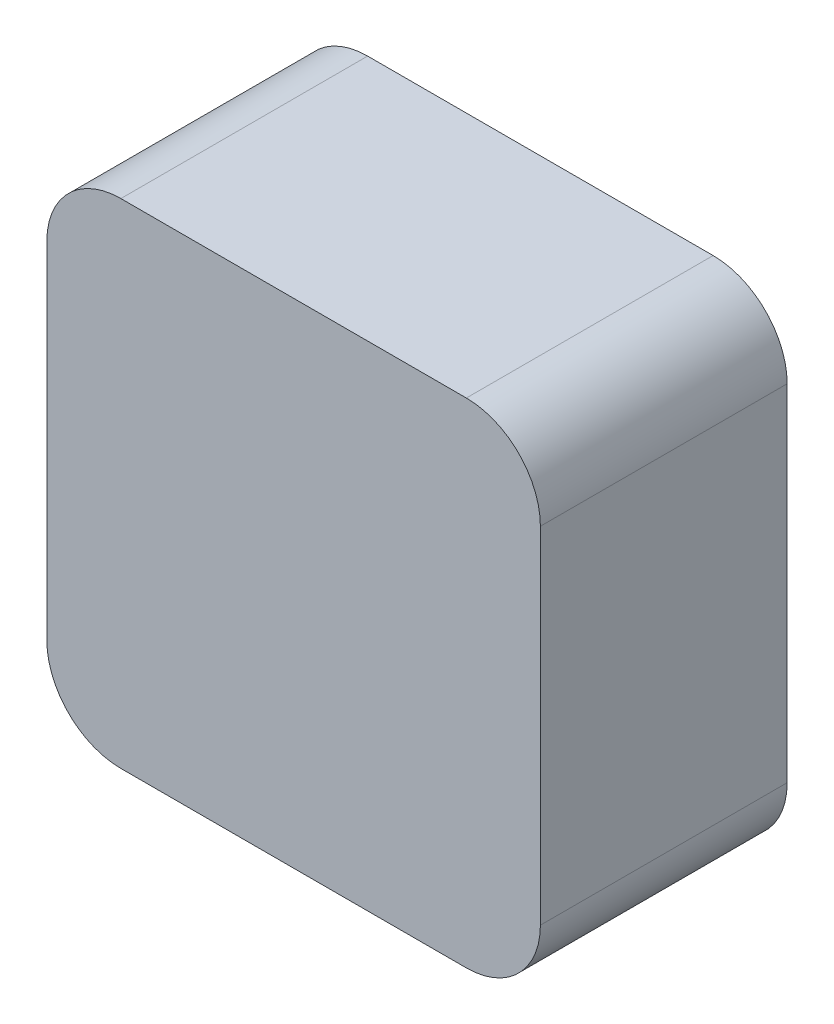
SolidWorks part; units mm, degrees
ref_plane "Front Plane" through (0, 0, 0) normal (0, 0, 1) x (1, 0, 0)
ref_plane "Top Plane" through (0, 0, 0) normal (0, 1, 0) x (1, 0, 0)
ref_plane "Right Plane" through (0, 0, 0) normal (1, 0, 0) x (0, 0, -1)
sketch "Sketch1" plane through (0, 0, 0) normal (0, 0, 1) x (1, 0, 0)
  line L1 (-145, 160.5) -> (-135, 160.5)
  line L2 (-145, 160.5) -> (-145, 150.5)
  line L3 (-145, 150.5) -> (-135, 150.5)
  line L4 (-135, 160.5) -> (-135, 150.5)
  circle A1 centre (-140, 155.5) radius 1.5
extrude "Boss-Extrude1" add sketch "Sketch1" along normal blind 5
fillet "Fillet1" radius 1.5 4 edges at (-145, 150.5, 2.5) (-145, 160.5, 2.5) (-135, 160.5, 2.5) (-135, 150.5, 2.5)
sketch "Sketch2" plane through (0, 0, 5) normal (0, 0, 1) x (1, 0, 0)
  circle A0 centre (-140, 155.5) radius 1.6
extrude "Boss-Extrude2" add sketch "Sketch2" against normal blind 1
sketch "Sketch3" plane through (0, 0, 0) normal (0, 0, -1) x (-1, 0, 0)
  circle A0 centre (140, 155.5) radius 2.25
extrude "Cut-Extrude1" cut sketch "Sketch3" against normal blind 3
